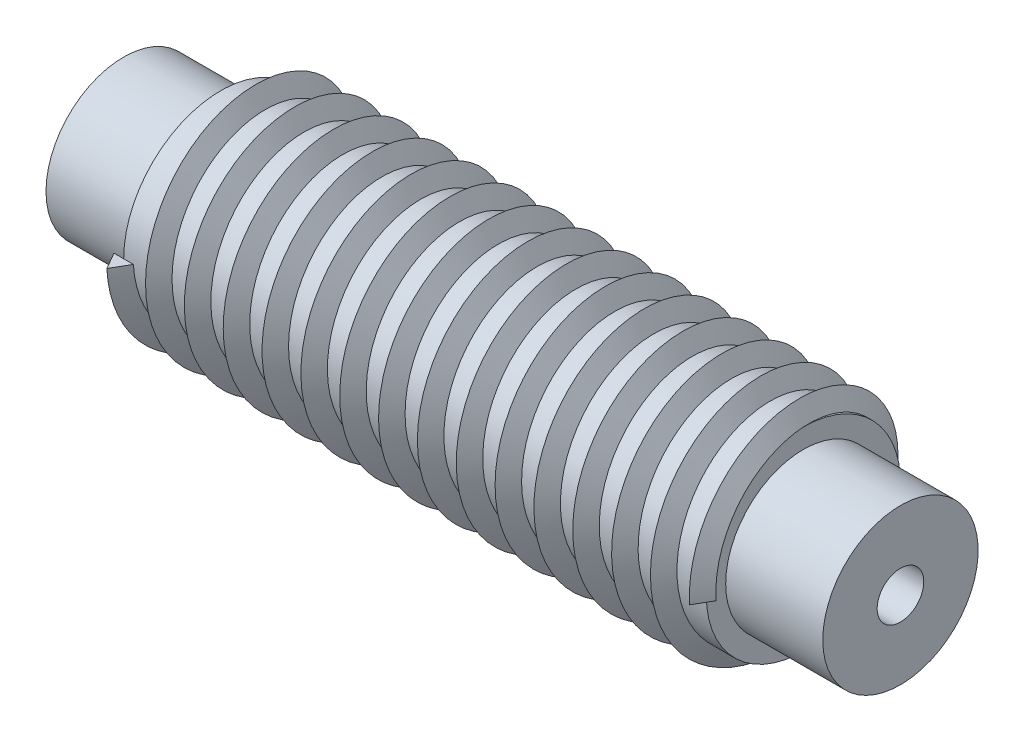
SolidWorks part; units mm, degrees
ref_plane "Front Plane" through (0, 0, 0) normal (0, 0, 1) x (1, 0, 0)
ref_plane "Top Plane" through (0, 0, 0) normal (0, 1, 0) x (1, 0, 0)
ref_plane "Right Plane" through (0, 0, 0) normal (1, 0, 0) x (0, 0, -1)
sketch "Sketch1" plane through (0, 0, 0) normal (0, 0, 1) x (1, 0, 0)
  line L0 (0, 0) -> (100, 0)
  line L1 (100, 0) -> (100, 10)
  line L2 (100, 10) -> (87.5, 10)
  line L3 (87.5, 10) -> (87.5, 12.5)
  line L4 (87.5, 12.5) -> (12.5, 12.5)
  line L5 (12.5, 12.5) -> (12.5, 10)
  line L6 (12.5, 10) -> (0, 10)
  line L7 (0, 10) -> (0, 0)
  dimension "D1" = 100
  dimension "D2" = 75
  dimension "D3" = 12.5
  dimension "D4" = 10
  dimension "D5" = 12.5
  dimension "D6" = 2.5
revolve "Revolve1" add sketch "Sketch1" angle 360 about L0
sketch "Sketch2" plane through (87.5, 0, 0) normal (1, 0, 0) x (0, 0, -1)
  circle A0 centre (0, 0) radius 12.5 construction
  circle A1 centre (0, 0) radius 12.5
curve "Helix/Spiral1" pitch 5 height 75 turns 15
sketch "Sketch3" plane through (0, 0, 0) normal (0, 1, 0) x (1, 0, 0)
  line L0 (12.5, -12.5) -> (13.75, -12.5)
  line L1 (12.5, -12.5) -> (87.5, -12.5) construction
  line L2 (13.75, -12.5) -> (12.5, -14.6651)
  line L3 (12.5, -14.6651) -> (11.25, -12.5)
  line L4 (11.25, -12.5) -> (12.5, -12.5)
  dimension "D1" = 2.5
  dimension "D2" = 300
  dimension "D3" = 120
  dimension "D4" = 1.25
sweep "Sweep2" add profiles "Sketch3" path "Helix/Spiral1"
sketch "Sketch4" plane through (100, 0, 0) normal (1, 0, 0) x (0, 0, -1)
  circle A0 centre (0, 0) radius 3
extrude "Cut-Extrude1" cut sketch "Sketch4" against normal blind 10
